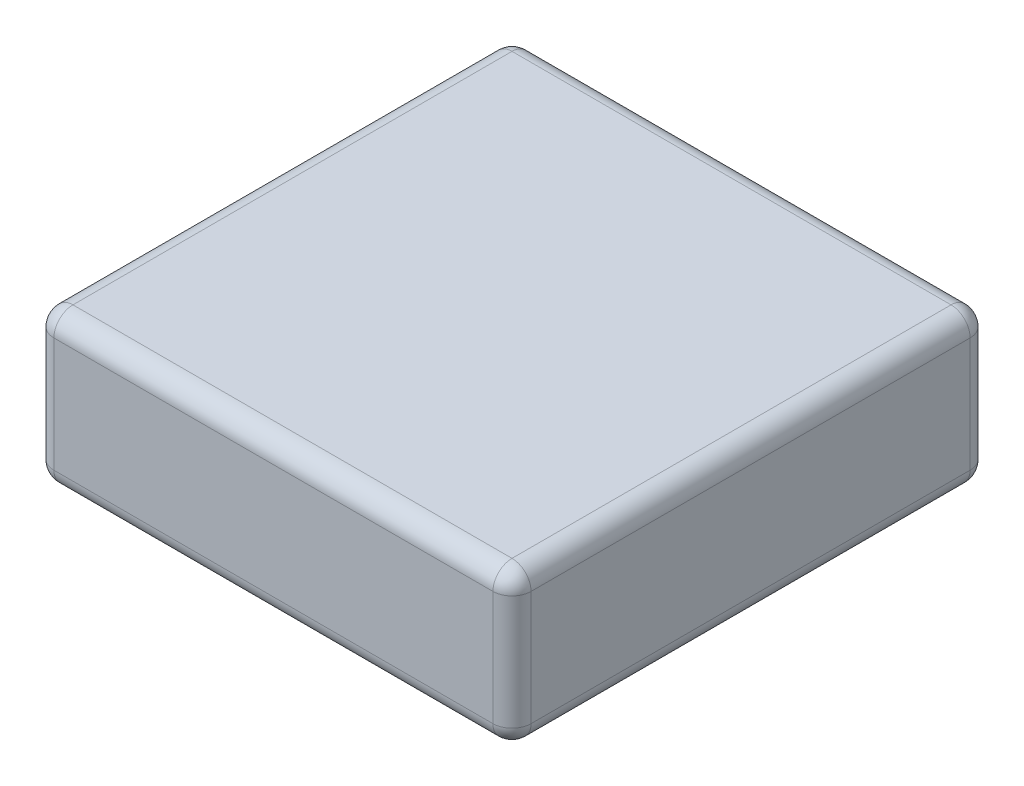
SolidWorks part; units mm, degrees
material "Duranickel(R) 301"
ref_plane "Front Plane" through (0, 0, 0) normal (0, 0, 1) x (1, 0, 0)
ref_plane "Top Plane" through (0, 0, 0) normal (0, 1, 0) x (1, 0, 0)
ref_plane "Right Plane" through (0, 0, 0) normal (1, 0, 0) x (0, 0, -1)
sketch "Sketch1" plane through (0, 0, 0) normal (0, 1, 0) x (1, 0, 0)
  line L1 (12.5, -12.5) -> (-12.5, -12.5)
  line L2 (12.5, -12.5) -> (12.5, 12.5)
  line L3 (12.5, 12.5) -> (-12.5, 12.5)
  line L4 (-12.5, -12.5) -> (-12.5, 12.5)
  line L5 (12.5, -12.5) -> (-12.5, 12.5) construction
  line L6 (12.5, 12.5) -> (-12.5, -12.5) construction
  point P0 (0, 0)
  dimension "D1" = 25
  dimension "D2" = 25
extrude "Boss-Extrude1" add sketch "Sketch1" along normal blind 8
fillet "Fillet1" radius 1 12 edges at (0, 0, 12.5) (12.5, 0, 0) (0, 0, -12.5) (-12.5, 0, 0) (0, 8, -12.5) (12.5, 8, 0) (0, 8, 12.5) (-12.5, 8, 0) (-12.5, 4, 12.5) (-12.5, 4, -12.5) (12.5, 4, 12.5) (12.5, 4, -12.5)
equation "\"D2@Sketch1\"=\"D1@Sketch1\""
